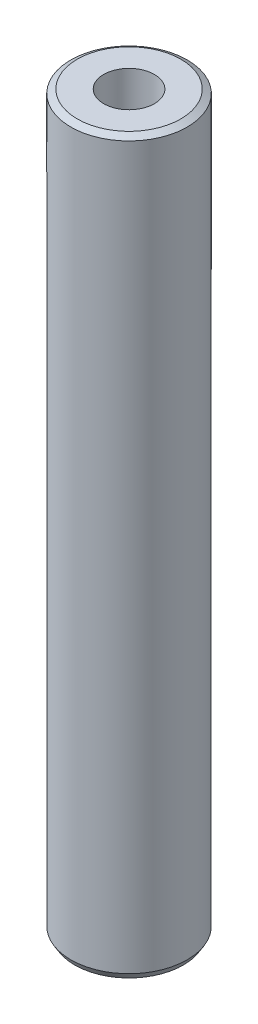
SolidWorks part; units mm, degrees
ref_plane "Front Plane" through (0, 0, 0) normal (0, 0, 1) x (1, 0, 0)
ref_plane "Top Plane" through (0, 0, 0) normal (0, 1, 0) x (1, 0, 0)
ref_plane "Right Plane" through (0, 0, 0) normal (1, 0, 0) x (0, 0, -1)
sketch "Sketch1" plane through (0, 0, 0) normal (0, 1, 0) x (1, 0, 0)
  circle A0 centre (0, 0) radius 22.5
  dimension "SHAFT_OD" = 45
extrude "Boss-Extrude1" add sketch "Sketch1" along normal blind 282.7502
sketch "Sketch2" plane through (0, 0, 0) normal (0, 1, 0) x (1, 0, 0)
  circle A0 centre (0, 0) radius 9.8021
  dimension "BORE_D" = 19.6043
extrude "Cut-Extrude1" cut sketch "Sketch2" along normal through all
chamfer "Chamfer1" distance 1.4753 angle 59.302 2 edges at (0, 282.7502, 22.5) (0, 0, 22.5) first distance on face at (0, 282.7502, 22.5) first distance on face at (0, 0, 9.8021)
